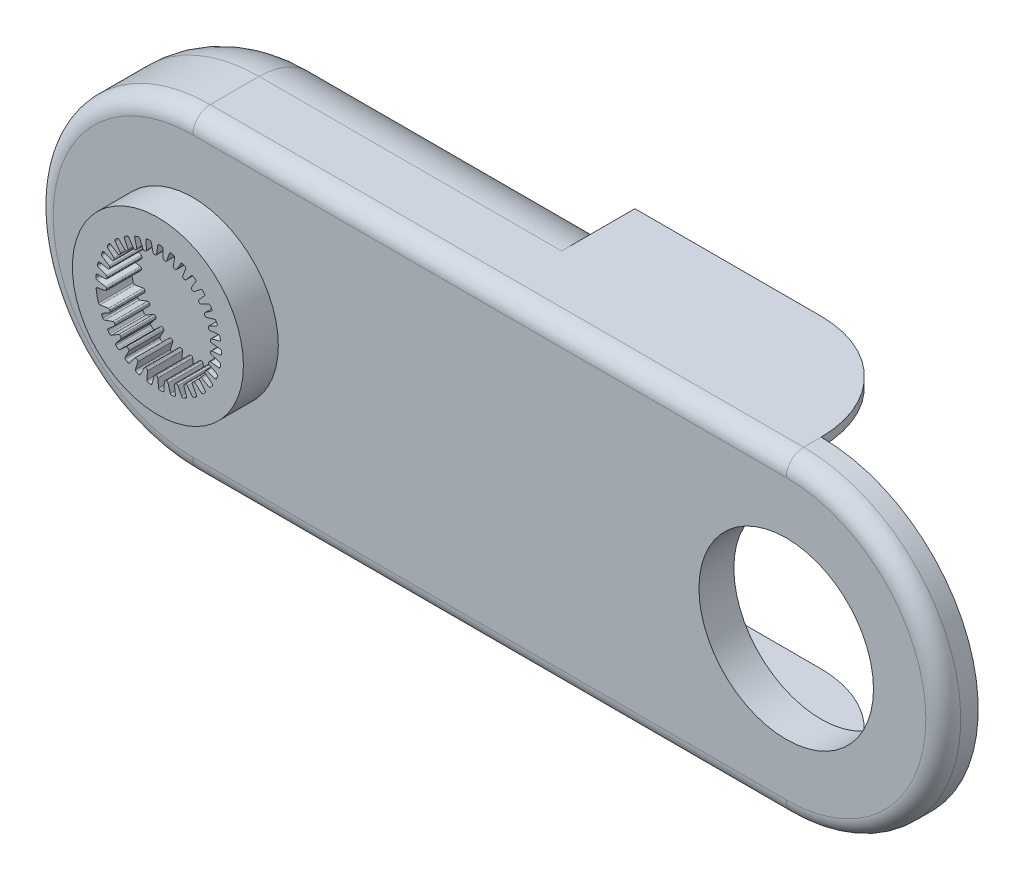
SolidWorks part; units mm, degrees
ref_plane "Front Plane" through (0, 0, 0) normal (0, 0, 1) x (1, 0, 0)
ref_plane "Top Plane" through (0, 0, 0) normal (0, 1, 0) x (1, 0, 0)
ref_plane "Right Plane" through (0, 0, 0) normal (1, 0, 0) x (0, 0, -1)
sketch "Sketch1" plane through (0, 0, 0) normal (0, 0, 1) x (1, 0, 0)
  line L0 (55, 0) -> (-55, 0) construction
  line L1 (-16.9691, -5.4979) -> (-14.565, -5.1246)
  line L2 (-14.1254, -5.3896) -> (-14.0498, -5.609)
  line L3 (-14.2318, -6.0878) -> (-16.2781, -7.2403)
  line L4 (-15.6283, -8.6059) -> (-13.3395, -7.7807)
  line L5 (-12.8575, -7.957) -> (-12.7414, -8.158)
  line L6 (-12.8287, -8.6627) -> (-14.6175, -10.1845)
  line L7 (-13.7191, -11.401) -> (-11.6298, -10.1543)
  line L8 (-11.1229, -10.2354) -> (-10.9707, -10.4105)
  line L9 (-10.96, -10.9225) -> (-12.4256, -12.7577)
  line L10 (-11.3116, -13.7804) -> (-9.4986, -12.158)
  line L11 (-8.9856, -12.1408) -> (-8.8027, -12.2837)
  line L12 (-8.6945, -12.7843) -> (-9.783, -14.8654)
  line L13 (-8.4943, -15.6568) -> (-7.0242, -13.7182)
  line L14 (-6.5239, -13.6035) -> (-6.3171, -13.7088)
  line L15 (-6.1154, -14.1796) -> (-6.7868, -16.4302)
  line L16 (-5.3708, -16.9611) -> (-4.2976, -14.7776)
  line L17 (-3.8283, -14.5696) -> (-3.6053, -14.6335)
  line L18 (-3.3174, -15.0571) -> (-3.5471, -17.3945)
  line L19 (-2.0557, -17.6455) -> (-1.4189, -15.2973)
  line L20 (-0.998, -15.0035) -> (-0.7668, -15.0238)
  line L21 (-0.4034, -15.3847) -> (-0.1828, -17.7229)
  line L22 (1.329, -17.6847) -> (1.5061, -15.2582)
  line L23 (1.8632, -14.8895) -> (2.094, -14.8652)
  line L24 (2.5196, -15.1502) -> (3.1822, -17.4034)
  line L25 (4.659, -17.0774) -> (4.3698, -14.6617)
  line L26 (4.65, -14.2316) -> (4.872, -14.1637)
  line L27 (5.3441, -14.3623) -> (6.4245, -16.4476)
  line L28 (7.8119, -15.8458) -> (7.0671, -13.5297)
  line L29 (7.2601, -13.054) -> (7.465, -12.9451)
  line L30 (7.9664, -13.0499) -> (9.4248, -14.8908)
  line L31 (10.6719, -14.0353) -> (9.4989, -11.9038)
  line L32 (9.5976, -11.4001) -> (9.7779, -11.254)
  line L33 (10.29, -11.2612) -> (12.073, -12.79)
  line L34 (13.1339, -11.7123) -> (11.5757, -9.8438)
  line L35 (11.5765, -9.3305) -> (11.7257, -9.1527)
  line L36 (12.2298, -9.0621) -> (14.2716, -10.2226)
  line L37 (15.1075, -8.9622) -> (13.2214, -7.4254)
  line L38 (13.1242, -6.9214) -> (13.2367, -6.7184)
  line L39 (13.7142, -6.5332) -> (15.94, -7.2828)
  line L40 (16.52, -5.8861) -> (14.3753, -4.7374)
  line L41 (14.1837, -4.2612) -> (14.2555, -4.0405)
  line L42 (14.6889, -3.7676) -> (17.0168, -4.0787)
  line L43 (17.3196, -2.597) -> (14.9951, -1.8786)
  line L44 (14.7162, -1.4477) -> (14.7445, -1.2173)
  line L45 (15.1179, -0.8668) -> (17.4624, -0.728)
  line L46 (17.477, 0.7843) -> (15.0581, 1.0459)
  line L47 (14.7021, 1.4157) -> (14.6859, 1.6472)
  line L48 (14.9856, 2.0626) -> (17.2605, 2.6462)
  line L49 (16.9862, 4.1334) -> (14.5619, 3.9288)
  line L50 (14.1419, 4.2238) -> (14.0818, 4.448)
  line L51 (14.2967, 4.9129) -> (16.4185, 5.9199)
  line L52 (15.8655, 7.3274) -> (13.5247, 6.6639)
  line L53 (13.0561, 6.8734) -> (12.9544, 7.082)
  line L54 (13.0766, 7.5794) -> (14.9673, 8.9727)
  line L55 (14.1559, 10.2489) -> (11.9847, 9.151)
  line L56 (11.4848, 9.2672) -> (11.3451, 9.4525)
  line L57 (11.3702, 9.9641) -> (12.9602, 11.6926)
  line L58 (11.9202, 12.7905) -> (9.9985, 11.2984)
  line L59 (9.4855, 11.3171) -> (9.3131, 11.4724)
  line L60 (9.2401, 11.9793) -> (10.4711, 13.9795)
  line L61 (9.2407, 14.8588) -> (7.6389, 13.0275)
  line L62 (7.1318, 12.9479) -> (6.9329, 13.0675)
  line L63 (6.7645, 13.5511) -> (7.5913, 15.7494)
  line L64 (6.2158, 16.3778) -> (4.9929, 14.2745)
  line L65 (4.5102, 14.0997) -> (4.2922, 14.1791)
  line L66 (4.0346, 14.6217) -> (4.4267, 16.9374)
  line L67 (2.9565, 17.2917) -> (2.1574, 14.9937)
  line L68 (1.7171, 14.73) -> (1.4878, 14.7663)
  line L69 (1.1505, 15.1517) -> (1.0936, 17.4997)
  line L70 (-0.4172, 17.567) -> (-0.7631, 15.1587)
  line L71 (-1.1451, 14.8159) -> (-1.377, 14.8078)
  line L72 (-1.7817, 15.1217) -> (-2.2855, 17.4156)
  line L73 (-3.7814, 17.1934) -> (-3.6615, 14.7634)
  line L74 (-3.971, 14.354) -> (-4.1972, 14.3018)
  line L75 (-4.6543, 14.5327) -> (-5.5866, 16.6884)
  line L76 (-7.0126, 16.1848) -> (-6.4312, 13.8224)
  line L77 (-6.6569, 13.3614) -> (-6.8689, 13.267)
  line L78 (-7.3617, 13.4065) -> (-8.6882, 15.3446)
  line L79 (-9.992, 14.5782) -> (-8.9705, 12.3701)
  line L80 (-9.1041, 11.8745) -> (-9.2942, 11.7414)
  line L81 (-9.8045, 11.7843) -> (-11.4765, 13.4337)
  line L82 (-12.61, 12.4326) -> (-11.1859, 10.46)
  line L83 (-11.2225, 9.948) -> (-11.3837, 9.7811)
  line L84 (-11.8929, 9.7258) -> (-13.8489, 11.0259)
  line L85 (-14.7706, 9.8269) -> (-12.9963, 8.1622)
  line L86 (-12.9345, 7.6527) -> (-13.0609, 7.458)
  line L87 (-13.5501, 7.3066) -> (-15.7182, 8.2096)
  line L88 (-16.3942, 6.8568) -> (-14.3349, 5.5613)
  line L89 (-14.177, 5.0729) -> (-14.264, 4.8577)
  line L90 (-14.7153, 4.6157) -> (-17.0159, 5.0884)
  line L91 (-17.4214, 3.6315) -> (-15.1526, 2.7527)
  line L92 (-14.9045, 2.3034) -> (-14.9488, 2.0756)
  line L93 (-15.3457, 1.7519) -> (-17.6942, 1.777)
  line L94 (-17.8142, 0.2694) -> (-15.4195, -0.1603)
  line L95 (-15.0901, -0.554) -> (-15.0901, -0.7861)
  line L96 (-15.418, -1.1795) -> (-17.7281, -1.6031)
  circle A0 centre (-0.372, 0) radius 24.5
  arc A1 (-18.0536, -2.0399) -> (-17.4139, -5.2165) centre (-0.1596, -0.0893) ccw
  arc A2 (-17.4139, -5.2165) -> (-16.9691, -5.4979) centre (-17.0305, -5.1026) ccw
  arc A3 (-14.1254, -5.3896) -> (-14.565, -5.1246) centre (-14.5036, -5.5198) ccw
  arc A4 (-14.2318, -6.0878) -> (-14.0498, -5.609) centre (-14.4281, -5.7393) ccw
  arc A5 (-16.2781, -7.2403) -> (-16.4437, -7.7593) centre (-16.0818, -7.5889) ccw
  arc A6 (-16.4437, -7.7593) -> (-16.1186, -8.4146) centre (-0.1596, -0.0893) ccw
  arc A7 (-16.1186, -8.4146) -> (-15.6283, -8.6059) centre (-15.764, -8.2296) ccw
  arc A8 (-12.8575, -7.957) -> (-13.3395, -7.7807) centre (-13.2039, -8.157) ccw
  arc A9 (-12.8287, -8.6627) -> (-12.7414, -8.158) centre (-13.0878, -8.358) ccw
  arc A10 (-14.6175, -10.1845) -> (-14.681, -10.7255) centre (-14.3583, -10.4892) ccw
  arc A11 (-14.681, -10.7255) -> (-14.2369, -11.3068) centre (-0.1596, -0.0893) ccw
  arc A12 (-14.2369, -11.3068) -> (-13.7191, -11.401) centre (-13.924, -11.0575) ccw
  arc A13 (-11.1229, -10.2354) -> (-11.6298, -10.1543) centre (-11.4248, -10.4978) ccw
  arc A14 (-10.96, -10.9225) -> (-10.9707, -10.4105) centre (-11.2726, -10.6729) ccw
  arc A15 (-12.4256, -12.7577) -> (-12.3847, -13.3009) centre (-12.1131, -13.0073) ccw
  arc A16 (-12.3847, -13.3009) -> (-11.8378, -13.7868) centre (-0.1596, -0.0893) ccw
  arc A17 (-11.8378, -13.7868) -> (-11.3116, -13.7804) centre (-11.5783, -13.4824) ccw
  arc A18 (-8.9856, -12.1408) -> (-9.4986, -12.158) centre (-9.2318, -12.456) ccw
  arc A19 (-8.6945, -12.7843) -> (-8.8027, -12.2837) centre (-9.049, -12.5989) ccw
  arc A20 (-9.783, -14.8654) -> (-9.6392, -15.3909) centre (-9.4286, -15.0508) ccw
  arc A21 (-9.6392, -15.3909) -> (-9.0097, -15.7634) centre (-0.1596, -0.0893) ccw
  arc A22 (-9.0097, -15.7634) -> (-8.4943, -15.6568) centre (-8.813, -15.4151) ccw
  arc A23 (-6.5239, -13.6035) -> (-7.0242, -13.7182) centre (-6.7055, -13.9599) ccw
  arc A24 (-6.1154, -14.1796) -> (-6.3171, -13.7088) centre (-6.4987, -14.0653) ccw
  arc A25 (-6.7868, -16.4302) -> (-6.5454, -16.9185) centre (-6.4035, -16.5446) ccw
  arc A26 (-6.5454, -16.9185) -> (-5.8563, -17.1641) centre (-0.1596, -0.0893) ccw
  arc A27 (-5.8563, -17.1641) -> (-5.3708, -16.9611) centre (-5.7297, -16.7847) ccw
  arc A28 (-3.8283, -14.5696) -> (-4.2976, -14.7776) centre (-3.9386, -14.9541) ccw
  arc A29 (-3.3174, -15.0571) -> (-3.6053, -14.6335) centre (-3.7155, -15.018) ccw
  arc A30 (-3.5471, -17.3945) -> (-3.2169, -17.8278) centre (-3.149, -17.4336) ccw
  arc A31 (-3.2169, -17.8278) -> (-2.4937, -17.9374) centre (-0.1596, -0.0893) ccw
  arc A32 (-2.4937, -17.9374) -> (-2.0557, -17.6455) centre (-2.4418, -17.5408) ccw
  arc A33 (-0.998, -15.0035) -> (-1.4189, -15.2973) centre (-1.0328, -15.402) ccw
  arc A34 (-0.4034, -15.3847) -> (-0.7668, -15.0238) centre (-0.8016, -15.4222) ccw
  arc A35 (-0.1828, -17.7229) -> (0.2239, -18.0853) centre (0.2154, -17.6853) ccw
  arc A36 (0.2239, -18.0853) -> (0.9548, -18.0548) centre (-0.1596, -0.0893) ccw
  arc A37 (0.9548, -18.0548) -> (1.329, -17.6847) centre (0.93, -17.6556) ccw
  arc A38 (1.8632, -14.8895) -> (1.5061, -15.2582) centre (1.905, -15.2873) ccw
  arc A39 (2.5196, -15.1502) -> (2.094, -14.8652) centre (2.1358, -15.263) ccw
  arc A40 (3.1822, -17.4034) -> (3.6506, -17.6814) centre (3.566, -17.2905) ccw
  arc A41 (3.6506, -17.6814) -> (4.3623, -17.5121) centre (-0.1596, -0.0893) ccw
  arc A42 (4.3623, -17.5121) -> (4.659, -17.0774) centre (4.2618, -17.1249) ccw
  arc A43 (4.65, -14.2316) -> (4.3698, -14.6617) centre (4.767, -14.6141) ccw
  arc A44 (5.3441, -14.3623) -> (4.872, -14.1637) centre (4.9889, -14.5463) ccw
  arc A45 (6.4245, -16.4476) -> (6.9374, -16.6312) centre (6.7797, -16.2636) ccw
  arc A46 (6.9374, -16.6312) -> (7.6036, -16.3292) centre (-0.1596, -0.0893) ccw
  arc A47 (7.6036, -16.3292) -> (7.8119, -15.8458) centre (7.4311, -15.9683) ccw
  arc A48 (7.2601, -13.054) -> (7.0671, -13.5297) centre (7.4479, -13.4072) ccw
  arc A49 (7.9664, -13.0499) -> (7.465, -12.9451) centre (7.6528, -13.2983) ccw
  arc A50 (9.4248, -14.8908) -> (9.9633, -14.9731) centre (9.7384, -14.6424) ccw
  arc A51 (9.9633, -14.9731) -> (10.5597, -14.5495) centre (-0.1596, -0.0893) ccw
  arc A52 (10.5597, -14.5495) -> (10.6719, -14.0353) centre (10.3215, -14.2282) ccw
  arc A53 (9.5976, -11.4001) -> (9.4989, -11.9038) centre (9.8493, -11.7109) ccw
  arc A54 (10.29, -11.2612) -> (9.7779, -11.254) centre (10.0297, -11.5649) ccw
  arc A55 (12.073, -12.79) -> (12.6173, -12.7681) centre (12.3334, -12.4864) ccw
  arc A56 (12.6173, -12.7681) -> (13.1219, -12.2385) centre (-0.1596, -0.0893) ccw
  arc A57 (13.1219, -12.2385) -> (13.1339, -11.7123) centre (12.8267, -11.9685) ccw
  arc A58 (11.5765, -9.3305) -> (11.5757, -9.8438) centre (11.8829, -9.5876) ccw
  arc A59 (12.2298, -9.0621) -> (11.7257, -9.1527) centre (12.0321, -9.4099) ccw
  arc A60 (14.2716, -10.2226) -> (14.8018, -10.0972) centre (14.4693, -9.8748) ccw
  arc A61 (14.8018, -10.0972) -> (15.196, -9.481) centre (-0.1596, -0.0893) ccw
  arc A62 (15.196, -9.481) -> (15.1075, -8.9622) centre (14.8548, -9.2723) ccw
  arc A63 (13.1242, -6.9214) -> (13.2214, -7.4254) centre (13.474, -7.1153) ccw
  arc A64 (13.7142, -6.5332) -> (13.2367, -6.7184) centre (13.5866, -6.9123) ccw
  arc A65 (15.94, -7.2828) -> (16.4365, -7.0586) centre (16.0677, -6.9037) ccw
  arc A66 (16.4365, -7.0586) -> (16.7059, -6.3785) centre (-0.1596, -0.0893) ccw
  arc A67 (16.7059, -6.3785) -> (16.52, -5.8861) centre (16.3311, -6.2387) ccw
  arc A68 (14.1837, -4.2612) -> (14.3753, -4.7374) centre (14.5642, -4.3848) ccw
  arc A69 (14.6889, -3.7676) -> (14.2555, -4.0405) centre (14.6359, -4.1641) ccw
  arc A70 (17.0168, -4.0787) -> (17.4613, -3.7638) centre (17.0698, -3.6822) ccw
  arc A71 (17.4613, -3.7638) -> (17.5961, -3.0448) centre (-0.1596, -0.0893) ccw
  arc A72 (17.5961, -3.0448) -> (17.3196, -2.597) centre (17.2015, -2.9792) ccw
  arc A73 (14.7162, -1.4477) -> (14.9951, -1.8786) centre (15.1133, -1.4964) ccw
  arc A74 (15.1179, -0.8668) -> (14.7445, -1.2173) centre (15.1415, -1.2661) ccw
  arc A75 (17.4624, -0.728) -> (17.8387, -0.3341) centre (17.4388, -0.3287) ccw
  arc A76 (17.8387, -0.3341) -> (17.8338, 0.3974) centre (-0.1596, -0.0893) ccw
  arc A77 (17.8338, 0.3974) -> (17.477, 0.7843) centre (17.434, 0.3866) ccw
  arc A78 (14.7021, 1.4157) -> (15.0581, 1.0459) centre (15.1011, 1.4436) ccw
  arc A79 (14.9856, 2.0626) -> (14.6859, 1.6472) centre (15.085, 1.6751) ccw
  arc A80 (17.2605, 2.6462) -> (17.5547, 3.1046) centre (17.1611, 3.0337) ccw
  arc A81 (17.5547, 3.1046) -> (17.4103, 3.8218) centre (-0.1596, -0.0893) ccw
  arc A82 (17.4103, 3.8218) -> (16.9862, 4.1334) centre (17.0199, 3.7348) ccw
  arc A83 (14.1419, 4.2238) -> (14.5619, 3.9288) centre (14.5283, 4.3274) ccw
  arc A84 (14.2967, 4.9129) -> (14.0818, 4.448) centre (14.4682, 4.5515) ccw
  arc A85 (16.4185, 5.9199) -> (16.6198, 6.426) centre (16.247, 6.2812) ccw
  arc A86 (16.6198, 6.426) -> (16.3413, 7.1024) centre (-0.1596, -0.0893) ccw
  arc A87 (16.3413, 7.1024) -> (15.8655, 7.3274) centre (15.9746, 6.9426) ccw
  arc A88 (13.0561, 6.8734) -> (13.5247, 6.6639) centre (13.4156, 7.0488) ccw
  arc A89 (13.0766, 7.5794) -> (12.9544, 7.082) centre (13.3139, 7.2574) ccw
  arc A90 (14.9673, 8.9727) -> (15.0684, 9.508) centre (14.73, 9.2947) ccw
  arc A91 (15.0684, 9.508) -> (14.6658, 10.1188) centre (-0.1596, -0.0893) ccw
  arc A92 (14.6658, 10.1188) -> (14.1559, 10.2489) centre (14.3364, 9.8919) ccw
  arc A93 (11.4848, 9.2672) -> (11.9847, 9.151) centre (11.8042, 9.5079) ccw
  arc A94 (11.3702, 9.9641) -> (11.3451, 9.4525) centre (11.6646, 9.6932) ccw
  arc A95 (12.9602, 11.6926) -> (12.9573, 12.2373) centre (12.6658, 11.9634) ccw
  arc A96 (12.9573, 12.2373) -> (12.4456, 12.7601) centre (-0.1596, -0.0893) ccw
  arc A97 (12.4456, 12.7601) -> (11.9202, 12.7905) centre (12.1655, 12.4745) ccw
  arc A98 (9.4855, 11.3171) -> (9.9985, 11.2984) centre (9.7532, 11.6144) ccw
  arc A99 (9.2401, 11.9793) -> (9.3131, 11.4724) centre (9.5807, 11.7697) ccw
  arc A100 (10.4711, 13.9795) -> (10.3643, 14.5136) centre (10.1304, 14.1891) ccw
  arc A101 (10.3643, 14.5136) -> (9.7623, 14.9292) centre (-0.1596, -0.0893) ccw
  arc A102 (9.7623, 14.9292) -> (9.2407, 14.8588) centre (9.5418, 14.5954) ccw
  arc A103 (7.1318, 12.9479) -> (7.6389, 13.0275) centre (7.3379, 13.2908) ccw
  arc A104 (6.7645, 13.5511) -> (6.9329, 13.0675) centre (7.1389, 13.4103) ccw
  arc A105 (7.5913, 15.7494) -> (7.3846, 16.2534) centre (7.2169, 15.8902) ccw
  arc A106 (7.3846, 16.2534) -> (6.7143, 16.5464) centre (-0.1596, -0.0893) ccw
  arc A107 (6.7143, 16.5464) -> (6.2158, 16.3778) centre (6.5616, 16.1768) ccw
  arc A108 (4.5102, 14.0997) -> (4.9929, 14.2745) centre (4.6471, 14.4756) ccw
  arc A109 (4.0346, 14.6217) -> (4.2922, 14.1791) centre (4.429, 14.5549) ccw
  arc A110 (4.4267, 16.9374) -> (4.1276, 17.3926) centre (4.0323, 17.0042) ccw
  arc A111 (4.1276, 17.3926) -> (3.4138, 17.5524) centre (-0.1596, -0.0893) ccw
  arc A112 (3.4138, 17.5524) -> (2.9565, 17.2917) centre (3.3343, 17.1604) ccw
  arc A113 (1.7171, 14.73) -> (2.1574, 14.9937) centre (1.7796, 15.1251) ccw
  arc A114 (1.1505, 15.1517) -> (1.4878, 14.7663) centre (1.5504, 15.1614) ccw
  arc A115 (1.0936, 17.4997) -> (0.7131, 17.8895) centre (0.6937, 17.49) ccw
  arc A116 (0.7131, 17.8895) -> (-0.0181, 17.9101) centre (-0.1596, -0.0893) ccw
  arc A117 (-0.0181, 17.9101) -> (-0.4172, 17.567) centre (-0.0212, 17.5101) ccw
  arc A118 (-1.1451, 14.8159) -> (-0.7631, 15.1587) centre (-1.1591, 15.2156) ccw
  arc A119 (-1.7817, 15.1217) -> (-1.377, 14.8078) centre (-1.391, 15.2075) ccw
  arc A120 (-2.2855, 17.4156) -> (-2.7334, 17.7257) centre (-2.6762, 17.3298) ccw
  arc A121 (-2.7334, 17.7257) -> (-3.4552, 17.6064) centre (-0.1596, -0.0893) ccw
  arc A122 (-3.4552, 17.6064) -> (-3.7814, 17.1934) centre (-3.3819, 17.2132) ccw
  arc A123 (-3.971, 14.354) -> (-3.6615, 14.7634) centre (-4.061, 14.7437) ccw
  arc A124 (-4.6543, 14.5327) -> (-4.1972, 14.3018) centre (-4.2871, 14.6915) ccw
  arc A125 (-5.5866, 16.6884) -> (-6.0854, 16.9073) centre (-5.9537, 16.5296) ccw
  arc A126 (-6.0854, 16.9073) -> (-6.7711, 16.6525) centre (-0.1596, -0.0893) ccw
  arc A127 (-6.7711, 16.6525) -> (-7.0126, 16.1848) centre (-6.6242, 16.2804) ccw
  arc A128 (-6.6569, 13.3614) -> (-6.4312, 13.8224) centre (-6.8196, 13.7268) ccw
  arc A129 (-7.3617, 13.4065) -> (-6.8689, 13.267) centre (-7.0316, 13.6324) ccw
  arc A130 (-8.6882, 15.3446) -> (-9.2196, 15.4643) centre (-9.0183, 15.1187) ccw
  arc A131 (-9.2196, 15.4643) -> (-9.8441, 15.0833) centre (-0.1596, -0.0893) ccw
  arc A132 (-9.8441, 15.0833) -> (-9.992, 14.5782) centre (-9.6289, 14.7462) ccw
  arc A133 (-9.1041, 11.8745) -> (-8.9705, 12.3701) centre (-9.3335, 12.2021) ccw
  arc A134 (-9.8045, 11.7843) -> (-9.2942, 11.7414) centre (-9.5236, 12.069) ccw
  arc A135 (-11.4765, 13.4337) -> (-12.021, 13.4498) centre (-11.7574, 13.1489) ccw
  arc A136 (-12.021, 13.4498) -> (-12.5613, 12.9567) centre (-0.1596, -0.0893) ccw
  arc A137 (-12.5613, 12.9567) -> (-12.61, 12.4326) centre (-12.2857, 12.6668) ccw
  arc A138 (-11.2225, 9.948) -> (-11.1859, 10.46) centre (-11.5103, 10.2259) ccw
  arc A139 (-11.8929, 9.7258) -> (-11.3837, 9.7811) centre (-11.6715, 10.0589) ccw
  arc A140 (-13.8489, 11.0259) -> (-14.3864, 10.9378) centre (-14.0703, 10.6928) ccw
  arc A141 (-14.3864, 10.9378) -> (-14.8227, 10.3506) centre (-0.1596, -0.0893) ccw
  arc A142 (-14.8227, 10.3506) -> (-14.7706, 9.8269) centre (-14.4969, 10.1186) ccw
  arc A143 (-12.9345, 7.6527) -> (-12.9963, 8.1622) centre (-13.27, 7.8705) ccw
  arc A144 (-13.5501, 7.3066) -> (-13.0609, 7.458) centre (-13.3963, 7.6759) ccw
  arc A145 (-15.7182, 8.2096) -> (-16.2291, 8.0206) centre (-15.872, 7.8404) ccw
  arc A146 (-16.2291, 8.0206) -> (-16.5454, 7.361) centre (-0.1596, -0.0893) ccw
  arc A147 (-16.5454, 7.361) -> (-16.3942, 6.8568) centre (-16.1812, 7.1954) ccw
  arc A148 (-14.177, 5.0729) -> (-14.3349, 5.5613) centre (-14.5479, 5.2227) ccw
  arc A149 (-14.7153, 4.6157) -> (-14.264, 4.8577) centre (-14.6348, 5.0075) ccw
  arc A150 (-17.0159, 5.0884) -> (-17.4813, 4.8054) centre (-17.0964, 4.6966) ccw
  arc A151 (-17.4813, 4.8054) -> (-17.6659, 4.0975) centre (-0.1596, -0.0893) ccw
  arc A152 (-17.6659, 4.0975) -> (-17.4214, 3.6315) centre (-17.2769, 4.0045) ccw
  arc A153 (-14.9045, 2.3034) -> (-15.1526, 2.7527) centre (-15.2971, 2.3797) ccw
  arc A154 (-15.3457, 1.7519) -> (-14.9488, 2.0756) centre (-15.3414, 2.1519) ccw
  arc A155 (-17.6942, 1.777) -> (-18.097, 1.4103) centre (-17.6984, 1.377) ccw
  arc A156 (-18.097, 1.4103) -> (-18.1432, 0.6803) centre (-0.1596, -0.0893) ccw
  arc A157 (-18.1432, 0.6803) -> (-17.8142, 0.2694) centre (-17.7435, 0.6632) ccw
  arc A158 (-15.0901, -0.554) -> (-15.4195, -0.1603) centre (-15.4901, -0.554) ccw
  arc A159 (-15.418, -1.1795) -> (-15.0901, -0.7861) centre (-15.4901, -0.7861) ccw
  arc A160 (-17.7281, -1.6031) -> (-18.0536, -2.0399) centre (-17.656, -1.9965) ccw
  dimension "D1" = 49
extrude "Boss-Extrude1" add sketch "Sketch1" along normal blind 10
sketch "Sketch6" plane through (0, 0, 0) normal (0, 0, 1) x (1, 0, 0)
  line L0 (-0.372, 0) -> (169.628, 0) construction
  line L1 (-0.372, 45) -> (169.628, 45)
  line L2 (169.628, -45) -> (-0.372, -45)
  arc A1 (169.628, -45) -> (169.628, 45) centre (169.628, 0) ccw
  arc A2 (-0.372, 45) -> (-0.372, -45) centre (-0.372, 0) ccw
  dimension "D1" = 170
  dimension "D2" = 90
extrude "Boss-Extrude3" add sketch "Sketch6" against normal blind 40
sketch "Sketch7" plane through (0, 0, -40) normal (0, 0, -1) x (-1, 0, 0)
  line L6 (-174.2492, 0) -> (0, 0) construction
  line L7 (-169.628, 42.5) -> (-91.4373, 42.5)
  line L8 (-257.0612, 42.5) -> (-257.0612, -42.5)
  line L9 (-169.628, -42.5) -> (-91.4373, -42.5)
  line L10 (-91.4373, 42.5) -> (-91.4373, -42.5)
  line L11 (-257.0612, 42.5) -> (-91.4373, -42.5) construction
  line L12 (-257.0612, -42.5) -> (-91.4373, 42.5) construction
  line L13 (-169.628, 45) -> (-169.628, 42.5)
  line L14 (-169.628, 45) -> (-257.0612, 45)
  line L15 (-257.0612, 45) -> (-257.0612, 42.5)
  line L16 (-169.628, -45) -> (-169.628, -42.5)
  line L17 (-169.628, -45) -> (-257.0612, -45)
  line L18 (-257.0612, -45) -> (-257.0612, -42.5)
  point P0 (-174.2492, 0)
  dimension "D1" = 85
extrude "Cut-Extrude3" cut sketch "Sketch7" against normal blind 30
fillet "Fillet12" radius 5 4 edges at (-45.372, 0, 0) (84.628, -45, 0) (84.628, 45, 0) (214.628, 0, 0)
fillet "Fillet14" radius 30 2 edges at (169.628, -43.75, -40) (169.628, 43.75, -40)
sketch "Sketch8" plane through (0, 0, -40) normal (0, 0, -1) x (-1, 0, 0)
  line L0 (-139.628, 45) -> (0.372, 45) construction
  line L1 (-86.2755, 45) -> (62.0003, 45)
  line L2 (-86.2755, 45) -> (-86.2755, -45)
  line L3 (-86.2755, -45) -> (62.0003, -45)
  line L4 (62.0003, 45) -> (62.0003, -45)
  line L5 (0.372, -45) -> (-139.628, -45) construction
extrude "Cut-Extrude4" cut sketch "Sketch8" against normal blind 1
fillet "Fillet16" radius 20 3 edges at (42.9518, -45, -39) (-45.372, 0, -39) (42.9518, 45, -39)
sketch "Sketch9" plane through (0, 0, -10) normal (0, 0, -1) x (-1, 0, 0)
  circle A0 centre (-169.628, 0) radius 25
extrude "Cut-Extrude5" cut sketch "Sketch9" against normal through all
